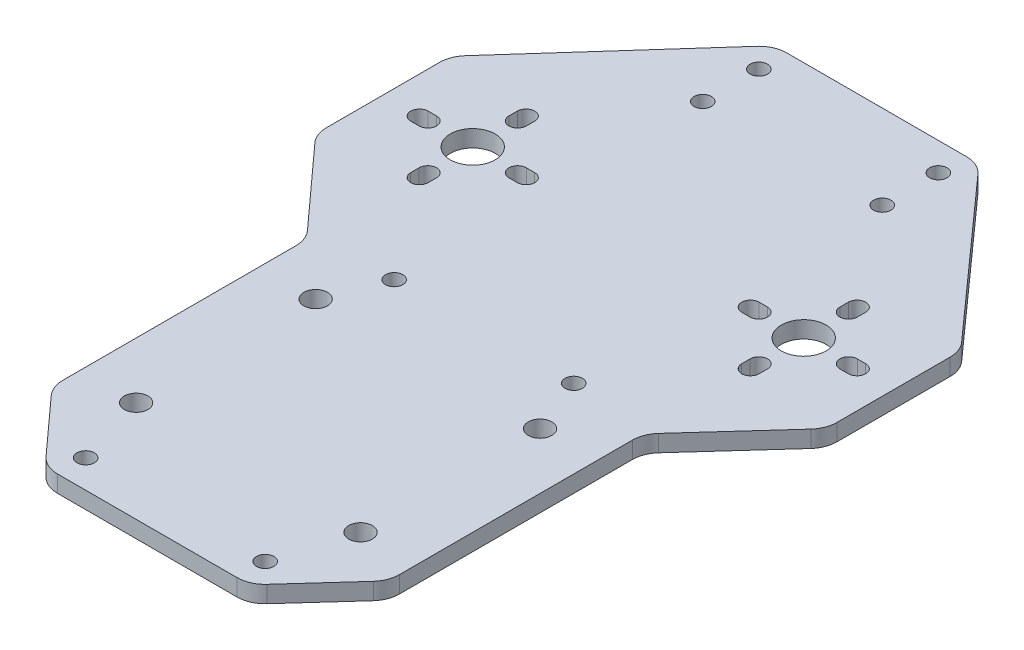
SolidWorks part; units mm, degrees
material "Thornel Mat VMA"
ref_plane "Front Plane" through (0, 0, 0) normal (0, 0, 1) x (1, 0, 0)
ref_plane "Top Plane" through (0, 0, 0) normal (0, 1, 0) x (1, 0, 0)
ref_plane "Right Plane" through (0, 0, 0) normal (1, 0, 0) x (0, 0, -1)
sketch "Sketch1" plane through (0, 0, 0) normal (0, 1, 0) x (1, 0, 0)
  line L0 (0, 0) -> (0, -82.5) construction
  line L1 (29.5, 0) -> (0, 0) construction
  line L2 (37.5, 0) -> (39, 0) construction
  line L3 (37.5, 1.55) -> (39, 1.55)
  line L4 (37.5, -1.55) -> (39, -1.55)
  line L5 (29.5, -8) -> (29.5, -9.5) construction
  line L6 (31.05, -8) -> (31.05, -9.5)
  line L7 (27.95, -8) -> (27.95, -9.5)
  line L8 (21.5, 0) -> (20, 0) construction
  line L9 (21.5, -1.55) -> (20, -1.55)
  line L10 (21.5, 1.55) -> (20, 1.55)
  line L11 (29.5, 8) -> (29.5, 9.5) construction
  line L12 (27.95, 8) -> (27.95, 9.5)
  line L13 (31.05, 8) -> (31.05, 9.5)
  line L14 (-37.5, 0) -> (-39, 0) construction
  line L19 (16, -27.5) -> (-16, -27.5) construction
  line L22 (16, -27.5) -> (16, 27.5) construction
  line L25 (16, 27.5) -> (-16, 27.5) construction
  line L28 (-16, -27.5) -> (-16, 27.5) construction
  line L38 (16, -27.5) -> (-16, 27.5) construction
  line L41 (45.5, 42.5) -> (-45.5, 42.5)
  line L44 (45.5, 42.5) -> (45.5, -87.5)
  line L47 (45.5, -87.5) -> (-45.5, -87.5)
  line L50 (-45.5, 42.5) -> (-45.5, -87.5)
  line L59 (-959, -57) -> (49041, -57) construction
  line L65 (16, 27.5) -> (-16, -27.5) construction
  line L66 (-16, 37.5) -> (16, 37.5) construction
  line L67 (-16, 37.5) -> (-16, 27.5) construction
  line L69 (16, 37.5) -> (16, 27.5) construction
  line L74 (-16, -27.5) -> (-16, -82.5) construction
  line L75 (-16, -82.5) -> (16, -82.5) construction
  line L76 (16, -82.5) -> (16, -27.5) construction
  line L77 (-20, -37.5) -> (20, -37.5) construction
  line L78 (-20, -37.5) -> (-20, -69.5) construction
  line L79 (-20, -69.5) -> (20, -69.5) construction
  line L80 (20, -37.5) -> (20, -69.5) construction
  line L81 (-20, -37.5) -> (20, -69.5) construction
  line L82 (-20, -69.5) -> (20, -37.5) construction
  line L83 (-37.5, 1.55) -> (-39, 1.55)
  line L84 (-37.5, -1.55) -> (-39, -1.55)
  line L85 (-29.5, 8) -> (-29.5, 9.5) construction
  line L86 (-27.95, 8) -> (-27.95, 9.5)
  line L87 (-31.05, 8) -> (-31.05, 9.5)
  line L88 (-21.5, 0) -> (-20, 0) construction
  line L89 (-21.5, -1.55) -> (-20, -1.55)
  line L90 (-21.5, 1.55) -> (-20, 1.55)
  line L91 (-29.5, -8) -> (-29.5, -9.5) construction
  line L92 (-31.05, -8) -> (-31.05, -9.5)
  line L93 (-27.95, -8) -> (-27.95, -9.5)
  line L94 (0, -82.5) -> (0, -87.5) construction
  circle A0 centre (29.5, 0) radius 4
  arc A1 (37.5, 1.55) -> (37.5, -1.55) centre (37.5, 0) ccw
  arc A2 (39, -1.55) -> (39, 1.55) centre (39, 0) ccw
  arc A3 (31.05, -8) -> (27.95, -8) centre (29.5, -8) ccw
  arc A4 (27.95, -9.5) -> (31.05, -9.5) centre (29.5, -9.5) ccw
  arc A5 (21.5, -1.55) -> (21.5, 1.55) centre (21.5, 0) ccw
  arc A6 (20, 1.55) -> (20, -1.55) centre (20, 0) ccw
  arc A7 (27.95, 8) -> (31.05, 8) centre (29.5, 8) ccw
  arc A8 (31.05, 9.5) -> (27.95, 9.5) centre (29.5, 9.5) ccw
  circle A22 centre (16, 27.5) radius 1.55
  circle A23 centre (16, -27.5) radius 1.55
  circle A24 centre (-16, -27.5) radius 1.55
  circle A25 centre (-16, 27.5) radius 1.55
  circle A76 centre (-16, 37.5) radius 1.55
  circle A77 centre (16, 37.5) radius 1.55
  circle A78 centre (20, -69.5) radius 2.1
  circle A79 centre (-20, -69.5) radius 2.1
  circle A91 centre (-16, -82.5) radius 1.55
  circle A92 centre (16, -82.5) radius 1.55
  circle A93 centre (-20, -37.5) radius 2.1
  circle A94 centre (20, -37.5) radius 2.1
  arc A95 (-37.5, 1.55) -> (-37.5, -1.55) centre (-37.5, 0) cw
  arc A96 (-39, -1.55) -> (-39, 1.55) centre (-39, 0) cw
  arc A97 (-27.95, 8) -> (-31.05, 8) centre (-29.5, 8) cw
  arc A98 (-31.05, 9.5) -> (-27.95, 9.5) centre (-29.5, 9.5) cw
  arc A99 (-21.5, -1.55) -> (-21.5, 1.55) centre (-21.5, 0) cw
  arc A100 (-20, 1.55) -> (-20, -1.55) centre (-20, 0) cw
  arc A101 (-31.05, -8) -> (-27.95, -8) centre (-29.5, -8) cw
  arc A102 (-27.95, -9.5) -> (-31.05, -9.5) centre (-29.5, -9.5) cw
  circle A103 centre (-29.5, 0) radius 4
  point P1 (0, -53.5)
  point P8 (38.25, 0)
  point P18 (29.5, -8.75)
  point P25 (20.75, 0)
  point P32 (29.5, 8.75)
  point P37 (29.5, 0)
  point P46 (-38.25, 0)
  point P51 (0, 32.5)
  point P54 (-29.5, 8.75)
  point P61 (-20.75, 0)
  point P68 (-29.5, -8.75)
  dimension "D1" = 8
  dimension "D2" = 1.55
  dimension "D4" = 8
  dimension "D5" = 4
  dimension "D6" = 5
  dimension "D7" = 5
  dimension "D8" = 40
  dimension "D9" = 32
  dimension "D10" = 3.1
  dimension "D11" = 10
  dimension "D12" = 55
  dimension "D13" = 16
  dimension "D15" = 10
  dimension "D19" = 32
  dimension "D20" = 29.5
  dimension "D27" = 4.2
  dimension "D3" = 1.5
  dimension "D14" = 55
extrude "凸台-拉伸1" add sketch "Sketch1" along normal blind 3 contours L41 L50 L47 L44 A79 A78 A23 A22 A0 A2 L4 A1 L3 A4 L7 A3 L6 A6 L10 A5 L9 A8 L13 A7 L12 region at (0, 0, 22.7969)
sketch "草图8" plane through (0, 0, 0) normal (0, 1, 0) x (1, 0, 0)
  line L3 (45.5, 42.5) -> (45.5, 12)
  line L13 (0, 42.5) -> (0, -87.5) construction
  line L15 (45.5, 42.5) -> (-45.5, 42.5) construction
  line L16 (45.5, -87.5) -> (-45.5, -87.5) construction
  line L17 (18.237, 42.5) -> (45.5, 42.5)
  line L19 (18.237, 42.5) -> (45.5, 12)
  line L20 (45.5, 42.5) -> (45.5, -87.5) construction
  line L21 (45.5, 12) -> (45.5, -12) construction
  line L22 (45.5, -12) -> (30, -29.0997)
  line L23 (30, -29.0997) -> (30, -74.5)
  line L24 (30, -74.5) -> (18.2162, -87.5)
  line L25 (45.5, -12) -> (45.5, -87.5)
  line L27 (45.5, -87.5) -> (18.2162, -87.5)
  line L28 (45.5, 0) -> (29.5, 0) construction
  line L29 (-45.5, -87.5) -> (-18.2162, -87.5)
  line L30 (-30, -74.5) -> (-18.2162, -87.5)
  line L31 (-30, -29.0997) -> (-30, -74.5)
  line L32 (-45.5, -12) -> (-45.5, -87.5)
  line L33 (-45.5, -12) -> (-30, -29.0997)
  line L34 (-18.237, 42.5) -> (-45.5, 12)
  line L35 (-18.237, 42.5) -> (-45.5, 42.5)
  line L36 (-45.5, 42.5) -> (-45.5, 12)
  circle A1 centre (16, 37.5) radius 1.55 construction
  circle A2 centre (20, -37.5) radius 2.1 construction
  circle A3 centre (20, -69.5) radius 2.1 construction
  circle A4 centre (16, -82.5) radius 1.55 construction
  point P2 (45.5, -12)
  point P4 (18.237, -87.5)
  point P31 (45.5, -87.5)
  dimension "D1" = 5
  dimension "D2" = 10
  dimension "D3" = 5
  dimension "D4" = 5
  dimension "D5" = 12
extrude "切除-拉伸1" cut sketch "草图8" along normal up to next contours L21 | L35 L36 L34 | L33 L32 L29 L30 L31 | L3 L19 L17 | L25 L27 L24 L23 L22 region at (-37.2545, 0, 55.8586) region at (-36.4123, 0, -32.3333)
fillet "圆角1" radius 5 12 edges at (-45.5, 1.5, 12) (-45.5, 1.5, -12) (-18.237, 1.5, -42.5) (45.5, 1.5, -12) (45.5, 1.5, 12) (30, 1.5, 29.0997) (30, 1.5, 74.5) (18.2162, 1.5, 87.5) (-18.2162, 1.5, 87.5) (-30, 1.5, 74.5) (-30, 1.5, 29.0997) (18.237, 1.5, -42.5) first distance on face at (-45.5, 1.5, 0) first distance on face at (-31.8685, 1.5, -27.25) first distance on face at (0, 1.5, -42.5) first distance on face at (45.5, 1.5, 0) first distance on face at (37.75, 1.5, 20.5499) first distance on face at (30, 1.5, 51.7999) first distance on face at (24.1081, 1.5, 81) first distance on face at (0, 1.5, 87.5) first distance on face at (-24.1081, 1.5, 81) first distance on face at (-30, 1.5, 51.7999) first distance on face at (-37.75, 1.5, 20.5499) first distance on face at (31.8685, 1.5, -27.25)
